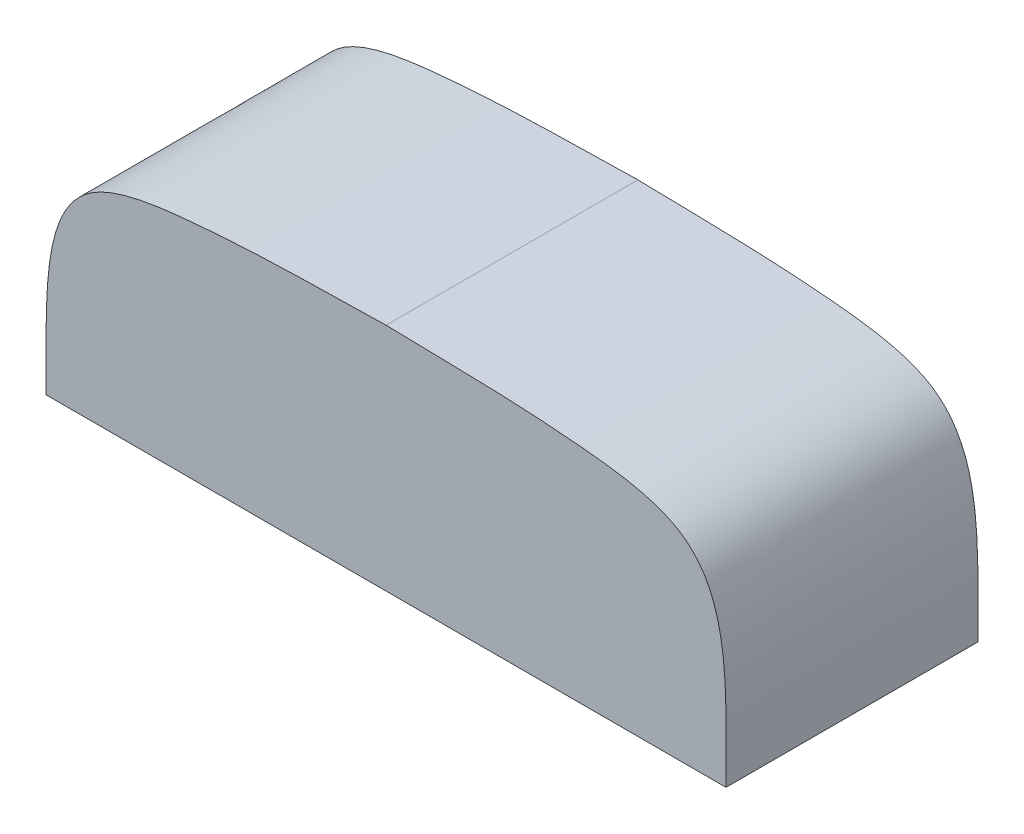
SolidWorks part; units mm, degrees
ref_plane "Front Plane" through (0, 0, 0) normal (0, 0, 1) x (1, 0, 0)
ref_plane "Top Plane" through (0, 0, 0) normal (0, 1, 0) x (1, 0, 0)
ref_plane "Right Plane" through (0, 0, 0) normal (1, 0, 0) x (0, 0, -1)
sketch "Sketch1" plane through (0, 0, 0) normal (0, 0, 1) x (1, 0, 0)
  line L1 (-342.9, 0) -> (342.9, 0)
  line L2 (0, 265.0008) -> (0, -43.3016) construction
  spline S0 degree 3 poles (0, 232.2583) (64.9766, 230.6344) (157.6161, 231.088) (351.0026, 205.1798) (342.883, 85.4029) (342.9, 0) knots 0 0 0 0 0.225226 0.33784 0.571999 0.571999 0.571999 0.571999
  spline S1 degree 3 poles (0, 232.2583) (-64.9766, 230.6344) (-157.6161, 231.088) (-351.0026, 205.1798) (-342.883, 85.4029) (-342.9, 0) knots 0 0 0 0 0.225226 0.33784 0.571999 0.571999 0.571999 0.571999
  point P8 (0, 0)
  dimension "D1" = 342.9
extrude "Boss-Extrude1" add sketch "Sketch1" along normal blind 127 and the other way blind 127
